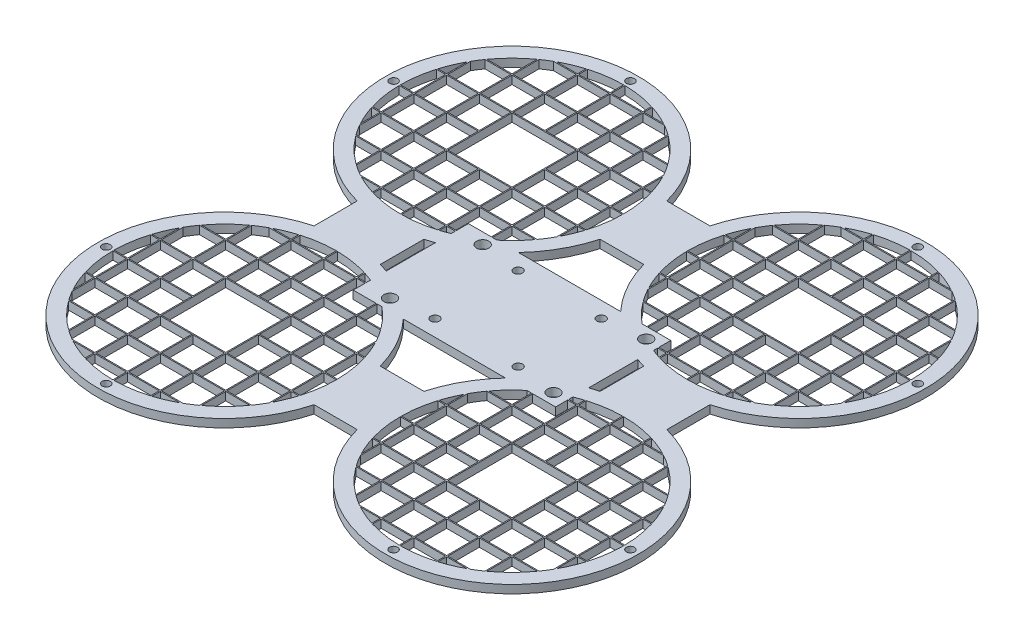
SolidWorks part; units mm, degrees
ref_plane "Front Plane" through (0, 0, 0) normal (0, 0, 1) x (1, 0, 0)
ref_plane "Top Plane" through (0, 0, 0) normal (0, 1, 0) x (1, 0, 0)
ref_plane "Right Plane" through (0, 0, 0) normal (1, 0, 0) x (0, 0, -1)
sketch "Sketch2" plane through (0, 0, 0) normal (0, 1, 0) x (1, 0, 0)
  circle A1 centre (0, 0) radius 41
  circle A2 centre (0, 0) radius 46
  point P208 (0, 0)
extrude "Boss-Extrude2" add sketch "Sketch2" along normal blind 3
sketch "Sketch4" plane through (0, 3, 0) normal (0, 1, 0) x (1, 0, 0)
  line L0 (0, 46) -> (0, 12)
  line L1 (12, 44.4072) -> (12, -44.4072)
  line L2 (24, 39.2428) -> (24, -39.2428)
  line L3 (36, 28.6356) -> (36, -28.6356)
  line L4 (-12, 44.4072) -> (-12, -44.4072)
  line L5 (-24, 39.2428) -> (-24, -32)
  line L6 (-36, 28.6356) -> (-36, -28.6356)
  line L7 (-46, 0) -> (-12, 0)
  line L8 (-44.4072, -12) -> (44.4072, -12)
  line L9 (-39.2428, -24) -> (39.2428, -24)
  line L10 (12, 0) -> (46, 0)
  line L11 (-44.4072, 12) -> (44.4072, 12)
  line L12 (-39.2428, 24) -> (39.2428, 24)
  line L13 (-28.6356, 36) -> (28.6356, 36)
  line L14 (-16, -36) -> (28.6356, -36)
  line L15 (0, -12) -> (0, -46)
  line L50 (-26.0661, -32) -> (-16, -32)
  line L52 (-26.0661, -32) -> (-26.0661, -37.902)
  line L60 (-16, -32) -> (-16, -43.1277)
  line L61 (-28.6356, -36) -> (-26.0661, -36) [skipped]
  circle A1 centre (0, 0) radius 46 construction
  circle A2 centre (0, 0) radius 46
  dimension "D1" = 4
  dimension "D2" = 4
extrude "Extrude-Thin5" add sketch "Sketch4" against normal blind 3 thin thin type one direction wall 0.4
sketch "Sketch5" plane through (0, 0, 0) normal (0, -1, 0) x (1, 0, 0)
  circle A0 centre (0, -43.4524) radius 1.5
  circle A3 centre (43.4524, 0) radius 1.5
  circle A4 centre (0, 43.4524) radius 1.5 [skipped]
  circle A5 centre (-43.4524, 0) radius 1.5 [skipped]
  point P11 (0, 0)
  dimension "D1" = 4
extrude "Cut-Extrude1" cut sketch "Sketch5" against normal blind 3
sketch "Sketch8" plane through (0, 3, 0) normal (0, 1, 0) x (1, 0, 0)
  line L1 (-16, -32) -> (-25.632, -32)
  line L2 (-16, -32) -> (-16, -37.7492)
  line L3 (-16, -37.7492) -> (-25.632, -37.7492)
  line L4 (-25.632, -32) -> (-25.632, -37.7492)
extrude "Boss-Extrude4" add sketch "Sketch8" against normal through all
sketch "Sketch9" plane through (0, 3, 0) normal (0, 1, 0) x (1, 0, 0)
  circle A3 centre (-22.2697, -36.1812) radius 2.25
extrude "Cut-Extrude3" cut sketch "Sketch9" against normal through all
ref_plane "Plane1" through (-52.73, 0, 0) normal (1, 0, 0) x (0, 0, -1)
mirror "Mirror1" about plane through (-52.73, 0, 0) normal (1, 0, 0) of bodies 159
sketch "Sketch10" plane through (0, 3, 0) normal (0, 1, 0) x (1, 0, 0)
  line L0 (-66.2554, 12) -> (-69.06, 12) construction
  line L1 (-63.5152, 12) -> (-41.7915, 12)
  line L2 (-63.5152, 12) -> (-63.5152, -12.4)
  line L3 (-63.5152, -12.4) -> (-41.7915, -12.4)
  line L4 (-41.7915, 12) -> (-41.7915, -12.4)
  line L5 (-66.3801, -12.4) -> (-69.06, -12.4) construction
extrude "Boss-Extrude5" add sketch "Sketch10" against normal up to surface (3 mm away) up to face at (-22.2697, 0, 38.4312)
ref_plane "Plane2" through (0, 0, 52.73) normal (0, 0, 1) x (1, 0, 0)
mirror "Mirror2" about plane through (0, 0, 52.73) normal (0, 0, 1) of bodies 177
sketch "Sketch11" plane through (0, 3, 0) normal (0, 1, 0) x (1, 0, 0)
  line L0 (-93.06, -36.4) -> (-93.06, -39.0799) construction
  line L1 (-117.46, -41.6571) -> (-93.06, -41.6571)
  line L2 (-117.46, -41.6571) -> (-117.46, -63.409)
  line L3 (-117.46, -63.409) -> (-93.06, -63.409)
  line L4 (-93.06, -41.6571) -> (-93.06, -63.409)
  line L5 (-117.46, -36.4) -> (-117.46, -39.2046) construction
extrude "Boss-Extrude6" add sketch "Sketch11" against normal up to surface (3 mm away) up to face at (-52.73, 0, -0.0036)
sketch "Sketch12" plane through (0, 3, 0) normal (0, 1, 0) x (1, 0, 0)
  line L0 (12, -36.4) -> (12, -39.2046) construction
  line L1 (-12.4, -42.0227) -> (12, -42.0227)
  line L2 (-12.4, -42.0227) -> (-12.4, -63.5098)
  line L3 (-12.4, -63.5098) -> (12, -63.5098)
  line L4 (12, -42.0227) -> (12, -63.5098)
  line L5 (-12.4, -36.4) -> (-12.4, -39.0799) construction
extrude "Boss-Extrude7" add sketch "Sketch12" against normal up to surface (3 mm away) up to face at (-62.5401, 0, 52.73)
sketch "Sketch13" plane through (0, 0, 0) normal (0, -1, 0) x (1, 0, 0)
  line L1 (-89.86, 73.86) -> (-15.6, 73.86)
  line L2 (-89.86, 73.86) -> (-89.86, 31.6)
  line L3 (-89.86, 31.6) -> (-15.6, 31.6)
  line L4 (-15.6, 73.86) -> (-15.6, 31.6)
extrude "Boss-Extrude8" add sketch "Sketch13" against normal up to surface (3 mm away) up to face at (-52.73, 3, 52.73)
sketch "Sketch15" plane through (0, 0, 0) normal (0, -1, 0) x (1, 0, 0)
  line L0 (-89.86, 61.761) -> (-89.86, 43.699) construction
  circle A4 centre (-35.304, 37.4126) radius 1.6
  circle A5 centre (-65.804, 37.4125) radius 1.6
  circle A6 centre (-65.804, 67.9125) radius 1.6
  circle A7 centre (-35.304, 67.9126) radius 1.6
  dimension "D1" = 24.056
  dimension "D2" = 54.556
extrude "Cut-Extrude5" cut sketch "Sketch15" against normal up to next
ref_plane "Plane3" through (-31.0539, 23.8804, 37.4127) normal (0, 0, 1) x (1, 0, 0)
ref_plane "Plane4" through (-41.904, 7.6858, 53.1026) normal (0, 0, 1) x (1, 0, 0)
sketch "Sketch18" plane through (0, 0, 0) normal (0, -1, 0) x (1, 0, 0)
  circle A0 centre (-20.5541, 69.6627) radius 2.25 construction
  circle A1 centre (-20.5539, 35.6627) radius 2.25 construction
  circle A2 centre (-80.5539, 35.6624) radius 2.25 construction
  circle A3 centre (-80.5541, 69.6624) radius 2.25 construction
  circle A4 centre (-20.5541, 69.6627) radius 2.25
  circle A5 centre (-20.5539, 35.6627) radius 2.25
  circle A6 centre (-80.5539, 35.6624) radius 2.25
  circle A7 centre (-80.5541, 69.6624) radius 2.25
extrude "Cut-Extrude6" cut sketch "Sketch18" against normal up to next
